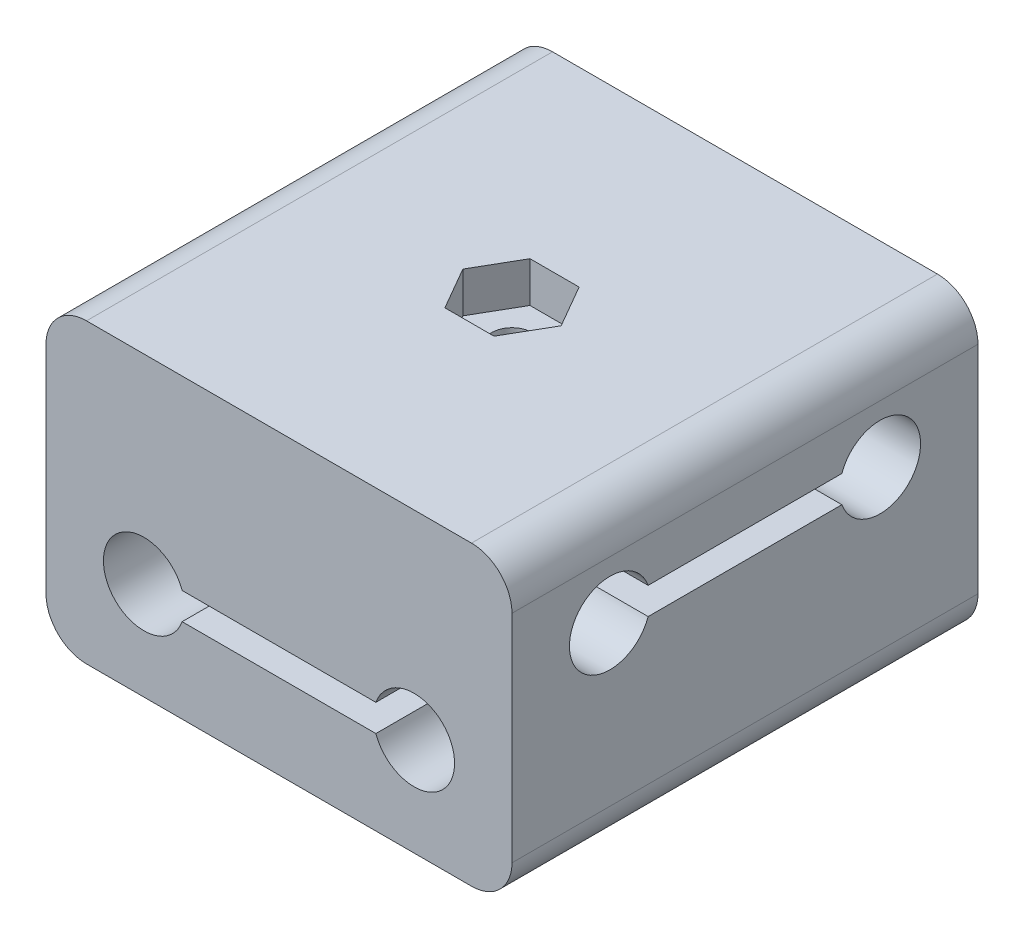
SolidWorks part; units mm, degrees
ref_plane "Front Plane" through (0, 0, 0) normal (0, 0, 1) x (1, 0, 0)
ref_plane "Top Plane" through (0, 0, 0) normal (0, 1, 0) x (1, 0, 0)
ref_plane "Right Plane" through (0, 0, 0) normal (1, 0, 0) x (0, 0, -1)
sketch "Sketch1" plane through (0, 0, 0) normal (0, 0, 1) x (1, 0, 0)
  line L0 (0, 0) -> (0, 11) construction
  line L1 (-17.25, 11) -> (17.25, 11)
  line L2 (-17.25, 11) -> (-17.25, -11)
  line L3 (-17.25, -11) -> (17.25, -11)
  line L4 (17.25, 11) -> (17.25, -11)
  line L5 (-17.25, 11) -> (17.25, -11) construction
  line L6 (-17.25, -11) -> (17.25, 11) construction
  line L8 (-7.1716, -2.75) -> (7.1716, -2.75)
  line L9 (-7.1716, -2.75) -> (-7.1716, -4.75) construction
  line L10 (-7.1716, -4.75) -> (7.1716, -4.75)
  line L11 (7.1716, -2.75) -> (7.1716, -4.75) construction
  line L12 (-7.1716, -2.75) -> (7.1716, -4.75) construction
  line L13 (-7.1716, -4.75) -> (7.1716, -2.75) construction
  circle A0 centre (-10, -3.75) radius 3
  circle A1 centre (10, -3.75) radius 3
  point P0 (0, 0)
  point P11 (0, -3.75)
  dimension "D3" = 6
  dimension "D4" = 2
  dimension "D1" = 22
  dimension "D2" = 34.5
  dimension "D5" = 6.25
  dimension "D6" = 7.25
  dimension "D7" = 7.25
  dimension "D8" = 20
extrude "Boss-Extrude1" add sketch "Sketch1" against normal blind 34.5 contours L4 L1 L2 L3 A1 L10 A0 L8 region at (0, 0.4715, 0)
sketch "Sketch2" plane through (17.25, 0, 0) normal (1, 0, 0) x (0, 0, -1)
  line L0 (17.25, -11) -> (17.25, 11) construction
  line L1 (34.5, -11) -> (0, -11) construction
  line L2 (34.5, 11) -> (0, 11) construction
  line L3 (24.4216, 2.75) -> (10.0784, 2.75)
  line L4 (24.4216, 2.75) -> (24.4216, 4.75) construction
  line L5 (10.0784, 2.75) -> (10.0784, 4.75) construction
  line L6 (24.4216, 4.75) -> (10.0784, 4.75)
  line L7 (24.4216, 2.75) -> (10.0784, 4.75) construction
  line L8 (10.0784, 2.75) -> (24.4216, 4.75) construction
  line L9 (0, 11) -> (0, -11) construction
  circle A0 centre (7.25, 3.75) radius 3
  circle A1 centre (27.25, 3.75) radius 3
  point P5 (17.25, 3.75)
  dimension "D1" = 6
  dimension "D2" = 2
  dimension "D3" = 7.25
  dimension "D4" = 6.25
extrude "Cut-Extrude1" cut sketch "Sketch2" against normal through all contours A0 | A1 L6 A0 L3 | A1 region at (17.25, 3.75, -17.25) region at (17.25, 3.75, -27.25) region at (17.25, 3.75, -7.25)
sketch "Sketch3" plane through (0, 11, 0) normal (0, 1, 0) x (1, 0, 0)
  line L1 (-1.8187, 20.4) -> (-3.6373, 17.25)
  line L2 (-3.6373, 17.25) -> (-1.8187, 14.1)
  line L3 (-1.8187, 14.1) -> (1.8187, 14.1)
  line L4 (1.8187, 14.1) -> (3.6373, 17.25)
  line L5 (3.6373, 17.25) -> (1.8187, 20.4)
  line L6 (1.8187, 20.4) -> (-1.8187, 20.4)
  line L7 (17.25, 34.5) -> (17.25, 0) construction
  circle A0 centre (0, 17.25) radius 3.15 construction
  circle A1 centre (0, 17.25) radius 1.5
  point P13 (17.25, 17.25)
  dimension "D2" = 3
  dimension "D1" = 6.3
extrude "Cut-Extrude2" cut sketch "Sketch3" against normal blind 3 contours L5 L6 L1 L2 L3 L4 A1 | A1 region at (0, 11, -20.3038) region at (0, 11, -17.25)
extrude "Cut-Extrude3" cut sketch "Sketch3<3>" against normal through all contours A1 region at (0, 11, -17.25)
sketch "Sketch3<3>" plane through (0, 11, 0) normal (0, 1, 0) x (1, 0, 0) same geometry as "Sketch3"
chamfer "Chamfer1" distance 2 angle 45 1 edges at (0, -11, -15.75)
fillet "Fillet1" radius 3 4 edges at (-17.25, -11, -17.25) (17.25, -11, -17.25) (17.25, 11, -17.25) (-17.25, 11, -17.25)
